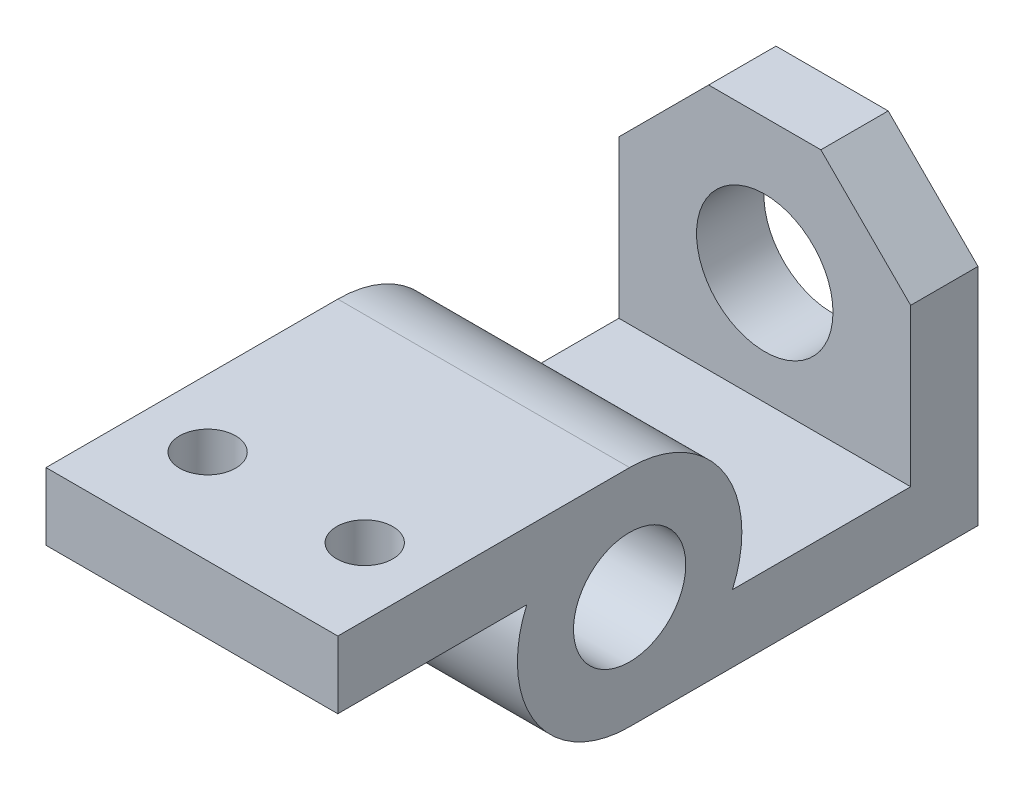
SolidWorks part; units mm, degrees
ref_plane "Front Plane" through (0, 0, 0) normal (0, 0, 1) x (1, 0, 0)
ref_plane "Top Plane" through (0, 0, 0) normal (0, 1, 0) x (1, 0, 0)
ref_plane "Right Plane" through (0, 0, 0) normal (1, 0, 0) x (0, 0, -1)
sketch "Sketch2" plane through (0, 0, 0) normal (1, 0, 0) x (0, 0, -1)
  line L0 (0, 31.75) -> (-82.55, 31.75)
  line L1 (-82.55, 31.75) -> (-82.55, 12.7)
  line L2 (-82.55, 12.7) -> (-29.0994, 12.7)
  line L3 (29.0994, -12.7) -> (79.502, -12.7)
  line L4 (79.502, -12.7) -> (79.502, 57.15)
  line L5 (79.502, 57.15) -> (98.552, 57.15)
  line L6 (98.552, 57.15) -> (98.552, -31.75)
  line L7 (98.552, -31.75) -> (0, -31.75)
  circle A0 centre (0, 0) radius 15.875
  arc A1 (0, 31.75) -> (29.0994, -12.7) centre (0, 0) cw
  arc A2 (0, -31.75) -> (-29.0994, 12.7) centre (0, 0) cw
  dimension "D1" = 31.75
  dimension "D2" = 31.75
  dimension "D3" = 31.75
  dimension "D4" = 19.05
  dimension "D5" = 98.552
  dimension "D6" = 181.102
  dimension "D7" = 19.05
  dimension "D8" = 88.9
  dimension "D9" = 19.05
extrude "Boss-Extrude1" add sketch "Sketch2" against normal blind 82.55 contours A2 L7 L6 L5 L4 L3 A1 L0 L1 L2 A0 region at (0, 3.5865, -22.9781)
sketch "Sketch4" plane through (0, 31.75, 0) normal (0, 1, 0) x (1, 0, 0)
  line L0 (0, 0) -> (0, -82.55) construction
  line L1 (-82.55, -82.55) -> (0, -82.55) construction
  circle A0 centre (-63.5, -55.88) radius 7.9375
  circle A1 centre (-19.05, -55.88) radius 7.9375
  dimension "D1" = 15.875
  dimension "D2" = 15.875
  dimension "D3" = 44.45
  dimension "D4" = 19.05
  dimension "D5" = 26.67
extrude "Cut-Extrude1" cut sketch "Sketch4" against normal through all
sketch "Sketch5" plane through (0, 0, -79.502) normal (0, 0, 1) x (1, 0, 0)
  line L0 (0, -12.7) -> (0, 57.15) construction
  line L1 (-82.55, 57.15) -> (0, 57.15) construction
  line L2 (-82.55, -12.7) -> (-82.55, 57.15) construction
  line L3 (0, -12.7) -> (0, 57.15)
  line L4 (-82.55, 57.15) -> (0, 57.15)
  line L5 (-82.55, -12.7) -> (-82.55, 57.15)
  line L6 (-82.55, 31.75) -> (-57.15, 57.15)
  line L7 (-25.4, 57.15) -> (0, 31.75)
  circle A0 centre (-41.275, 19.05) radius 19.304
  line M3 (0, 57.15) -> (-82.55, 57.15)
  line M4 (-82.55, 57.15) -> (-82.55, -12.7)
  dimension "D1" = 38.608
  dimension "D2" = 38.1
  dimension "D3" = 41.275
  dimension "D4" = 25.4
  dimension "D5" = 25.4
  dimension "D6" = 25.4
  dimension "D7" = 25.4
extrude "Cut-Extrude2" cut sketch "Sketch5" against normal through all contours L6 L4 M4 | L7 L3 M3 | A0 region at (-8.4667, 48.6833, -79.502) region at (-74.0833, 48.6833, -79.502) region at (-41.275, 19.05, -79.502)
